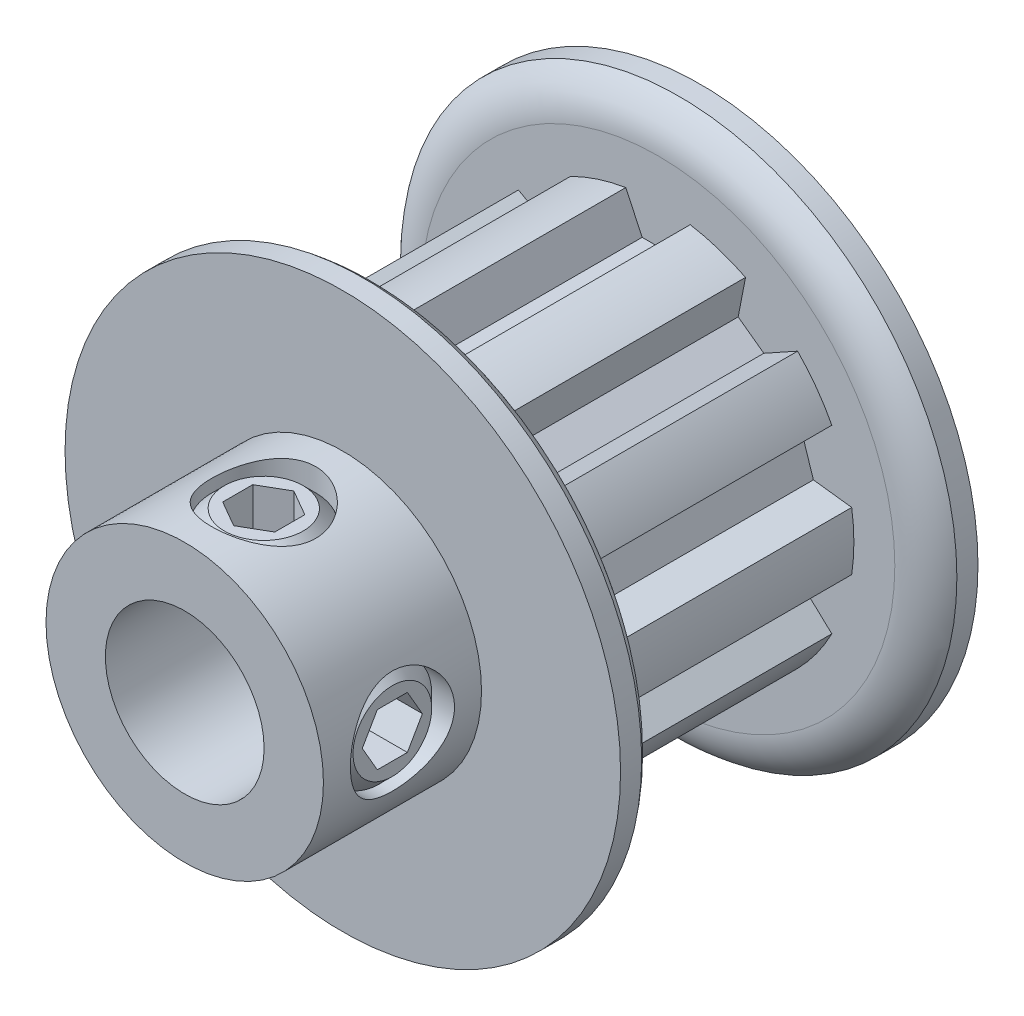
SolidWorks part; units mm, degrees
ref_plane "Front Plane" through (0, 0, 0) normal (0, 0, 1) x (1, 0, 0)
ref_plane "Top Plane" through (0, 0, 0) normal (0, 1, 0) x (1, 0, 0)
ref_plane "Right Plane" through (0, 0, 0) normal (1, 0, 0) x (0, 0, -1)
sketch "Sketch1" plane through (0, 0, 0) normal (0, 0, 1) x (1, 0, 0)
  line L0 (-1.2878, 7.7293) -> (-0.635, 6.3293)
  line L1 (-0.635, 6.3293) -> (0.635, 6.3293)
  line L2 (0.635, 6.3293) -> (1.2878, 7.7293)
  line L3 (-1.2878, 7.7293) -> (1.2878, 7.7293)
  line L4 (0, 0) -> (0, 6.3293) construction
  line L5 (0, 6.3293) -> (0, 8.6153) construction
  circle A0 centre (0, 0) radius 8.0899 construction
  circle A1 centre (0, 0) radius 11.1125 construction
  circle A2 centre (0, 0) radius 7.8359 construction
  point P6 (0, 7.7293)
  point P11 (0, 8.0899)
  point P13 (0, 11.1125)
  point P14 (0, 7.8359)
  dimension "D1" = 1.4
  dimension "PD" = 16.1798
  dimension "OD" = 22.225
  dimension "D3" = 1.27
  dimension "Gear OD" = 15.6718
  dimension "b" = 50
  dimension "hs" = 2.286
sketch "Sketch2" plane through (0, 0, 0) normal (1, 0, 0) x (0, 0, -1)
  line L0 (-10.3124, 3.175) -> (10.3124, 3.175)
  line L1 (-10.3124, 3.175) -> (-10.3124, 5.5499)
  line L2 (-10.3124, 5.5499) -> (-3.9878, 5.5499)
  line L3 (-3.9878, 5.5499) -> (-3.9878, 11.1125)
  line L4 (-3.9878, 11.1125) -> (-2.2987, 11.1125) construction
  line L5 (-2.2987, 11.1125) -> (-2.2987, 7.8359) construction
  line L6 (-2.2987, 7.8359) -> (8.6233, 7.8359)
  line L7 (8.6233, 7.8359) -> (8.6233, 11.1125) construction
  line L8 (8.6233, 11.1125) -> (10.3124, 11.1125) construction
  line L9 (10.3124, 11.1125) -> (10.3124, 3.175)
  line L10 (-10.3124, 0) -> (10.3124, 0) construction
  line L13 (-3.9878, 11.1125) -> (-3.1432, 11.1125)
  line L14 (-2.2987, 9.4742) -> (-2.2987, 7.8359)
  line L15 (8.6233, 7.8359) -> (8.6233, 9.4742)
  line L16 (9.4679, 11.1125) -> (10.3124, 11.1125)
  arc A0 (-2.2987, 9.4742) -> (-3.1432, 11.1125) centre (-4.31, 9.4742) ccw
  arc A1 (8.6233, 9.4742) -> (9.4679, 11.1125) centre (10.6346, 9.4742) cw
  point P12 (-2.2987, 9.4742)
  point P14 (-3.1432, 11.1125)
  point P20 (8.6233, 9.4742)
  point P21 (9.4679, 11.1125)
  point P25 (8.6233, 0)
  point P26 (-2.2987, 0)
  dimension "OA" = 20.6248
  dimension "Bore" = 6.35
  dimension "Hub Dia" = 11.0998
  dimension "Outside Width" = 14.3002
  dimension "Inside Width" = 10.922
revolve "Revolve1" add sketch "Sketch2" angle 360 mid plane about L10
sketch "Sketch3" plane through (0, 0, 0) normal (0, 0, 1) x (1, 0, 0)
  line L0 (-0.635, 6.3293) -> (0.635, 6.3293) construction
  line L1 (0.635, 6.3293) -> (1.2878, 7.7293) construction
  line L2 (-1.2878, 7.7293) -> (-0.635, 6.3293) construction
  line L3 (-0.635, 6.3293) -> (0.635, 6.3293)
  line L4 (0.635, 6.3293) -> (1.2878, 7.7293)
  line L5 (-1.2878, 7.7293) -> (-0.635, 6.3293)
  circle A0 centre (0, 0) radius 7.8359 construction
  arc A1 (1.2878, 7.7293) -> (-1.2878, 7.7293) centre (0, 0) ccw
extrude "Cut-Extrude1" cut sketch "Sketch3" against normal up to vertex (8.6233 mm away) from vertex up to point (0, 7.8359, -8.6233) starting at point (0, 7.8359, 2.2987)
fillet "Fillet1" [suppressed] radius 0.61
pattern_circular "CirPattern1" count 10 over 360 about axis through (0, 0, 10.3124) along (0, 0, 1) of "Cut-Extrude1", "Fillet1"
sketch "Sketch4" plane through (0, 0, 0) normal (0, 1, 0) x (1, 0, 0)
  line L0 (0, -3.9878) -> (0, -10.3124) construction
  circle A0 centre (0, -7.1501) radius 2.0828
  dimension "D1" = 4.1656
extrude "Cut-Extrude2" cut sketch "Sketch4" along normal through all
ref_plane "Plane1" through (0, 0, 7.1501) normal (0, 0, 1) x (1, 0, 0)
sketch "Sketch5" plane through (0, 0, 7.1501) normal (0, 0, 1) x (1, 0, 0)
  line L0 (0, 0) -> (0, 5.5499) construction
  line L1 (1.5748, 5.1443) -> (2.0828, 4.6363)
  line L2 (0, 5.1443) -> (1.5748, 5.1443)
  line L3 (0, 5.1443) -> (0, 3.175)
  line L4 (0, 3.175) -> (1.4478, 3.175)
  line L5 (2.0828, 4.6363) -> (2.0828, 3.81)
  line L6 (1.4478, 3.175) -> (2.0828, 3.81)
  circle A0 centre (0, 0) radius 5.5499 construction
  circle A1 centre (0, 0) radius 3.175 construction
  point P7 (2.0828, 3.175)
  point P9 (2.0828, 5.1443)
revolve "Revolve2" add sketch "Sketch5" angle 360 mid plane about L0
sketch "Sketch6" plane through (0, 5.1443, 0) normal (0, 1, 0) x (1, 0, 0)
  line L1 (0, -5.9476) -> (-1.0414, -6.5488)
  line L2 (-1.0414, -6.5488) -> (-1.0414, -7.7514)
  line L3 (-1.0414, -7.7514) -> (0, -8.3526)
  line L4 (0, -8.3526) -> (1.0414, -7.7514)
  line L5 (1.0414, -7.7514) -> (1.0414, -6.5488)
  line L6 (1.0414, -6.5488) -> (0, -5.9476)
  circle A0 centre (0, -7.1501) radius 1.0414 construction
  dimension "D1" = 2.0828
extrude "Cut-Extrude3" cut sketch "Sketch6" against normal blind 1.5621
pattern_circular "CirPattern2" count 2 every 90 of "Cut-Extrude2", "Revolve2", "Cut-Extrude3"
ref_plane "Contact Plane 1" through (0, 0, 10.3124) normal (0, 0, 1) x (1, 0, 0)
ref_plane "Contact Plane 2" through (0, 0, -10.3124) normal (0, 0, -1) x (-1, 0, 0)
ref_axis "Center Axis 1" through (0, 0, -10.3124) along (0, 0, 1)
equation "\"D1@Sketch6\" = \"D1@Sketch4\"/2"
equation "\"D1@Cut-Extrude3\" = \"D1@Sketch6\"*.75"
